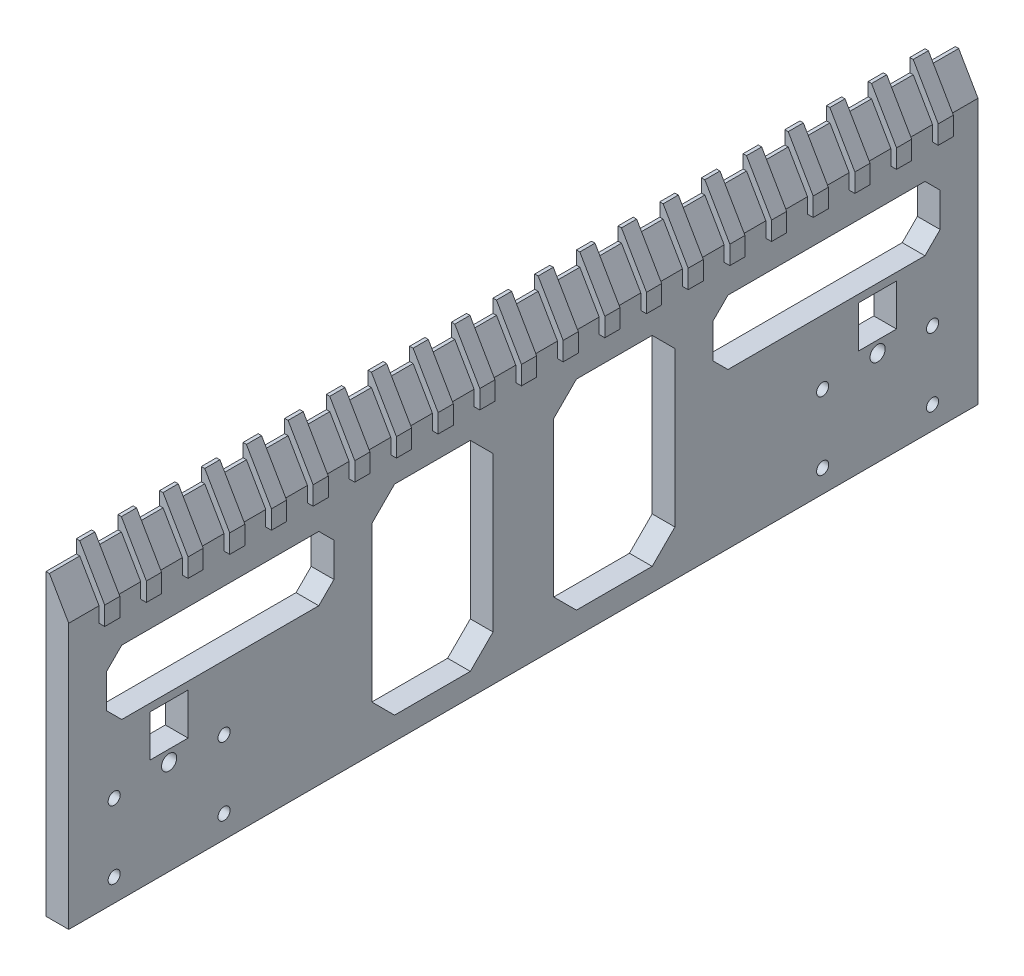
SolidWorks part; units mm, degrees
ref_plane "前视基准面" through (0, 0, 0) normal (0, 0, 1) x (1, 0, 0)
ref_plane "上视基准面" through (0, 0, 0) normal (0, 1, 0) x (1, 0, 0)
ref_plane "右视基准面" through (0, 0, 0) normal (1, 0, 0) x (0, 0, -1)
sketch "草图1" plane through (0, 0, 0) normal (1, 0, 0) x (0, 0, -1)
  line L1 (0, 0) -> (240, 0)
  line L2 (0, 0) -> (0, -70)
  line L3 (0, -70) -> (240, -70)
  line L4 (240, 0) -> (240, -70)
  dimension "D1" = 240
  dimension "D2" = 70
extrude "凸台-拉伸1" add sketch "草图1" along normal blind 6
sketch "草图3" plane through (6, 0, 0) normal (1, 0, 0) x (0, 0, -1)
  line L0 (120, 0) -> (120, -70) construction
  line L1 (14, -12) -> (66, -12)
  line L2 (10, -16) -> (10, -25)
  line L3 (14, -29) -> (66, -29)
  line L4 (70, -16) -> (70, -25)
  line L5 (240, 0) -> (0, 0) construction
  line L6 (0, -70) -> (240, -70) construction
  line L7 (0, 0) -> (0, -70) construction
  line L12 (10, -16) -> (14, -12)
  line L13 (10, -25) -> (14, -29)
  line L14 (66, -29) -> (70, -25)
  line L15 (66, -12) -> (70, -16)
  line L28 (80, -17.2) -> (86, -11.2)
  line L42 (86, -11.2) -> (106, -11.2)
  line L43 (80, -17.2) -> (80, -58)
  line L44 (86, -64) -> (106, -64)
  line L45 (112, -17.2) -> (112, -58)
  line L46 (106, -11.2) -> (112, -17.2)
  line L47 (106, -64) -> (112, -58)
  line L48 (80, -58) -> (86, -64)
  point P0 (10, -12)
  point P1 (70, -29)
  point P2 (10, -29)
  point P3 (70, -12)
  point P20 (80, -11.2)
  point P21 (112, -64)
  point P22 (80, -64)
  point P23 (112, -11.2)
  dimension "D1" = 10
  dimension "D2" = 12
  dimension "D3" = 17
  dimension "D4" = 60
  dimension "D5" = 11.2
  dimension "D6" = 6
  dimension "D7" = 52.8
  dimension "D12" = 80
  dimension "D13" = 8
  dimension "D14" = 32
extrude "切除-拉伸2" cut sketch "草图3" against normal through all
sketch "草图2" plane through (0, 0, 0) normal (1, 0, 0) x (0, 0, -1)
  line L0 (0, 0) -> (0, -70) construction
  line L1 (12, -46) -> (41, -46) construction
  line L2 (12, -46) -> (12, -64) construction
  line L3 (12, -64) -> (41, -64) construction
  line L4 (41, -46) -> (41, -64) construction
  line L5 (240, 0) -> (0, 0) construction
  line L6 (120, 0) -> (120, -70) construction
  circle A0 centre (12, -46) radius 1.55
  circle A1 centre (41, -64) radius 1.55
  circle A2 centre (41, -46) radius 1.55
  circle A3 centre (12, -64) radius 1.55
  dimension "D5" = 3.1
  dimension "D1" = 12
  dimension "D2" = 46
  dimension "D3" = 29
  dimension "D4" = 18
sketch "草图6" plane through (0, 0, 0) normal (0, 0, 1) x (1, 0, 0)
  line L0 (6, 0) -> (0, 0)
  line L1 (0, 0) -> (0, 8.8335)
  line L2 (0.9, 8.8335) -> (6, 0)
  line L3 (0, 8.8335) -> (0.9, 8.8335)
  line L4 (0, 8.8335) -> (0, 10.3923) construction
  line L5 (0, 10.3923) -> (0.9, 8.8335) construction
  dimension "D1" = 30
  dimension "D2" = 0.9
extrude "凸台-拉伸2" add sketch "草图6" against normal blind 240
ref_plane "基准面1" through (0, 0, -120) normal (0, 0, 1) x (1, 0, 0)
sketch "草图8" plane through (0, 0, -120) normal (0, 0, 1) x (1, 0, 0)
  line L0 (0, 10.3923) -> (0, 12.3335)
  line L1 (0.9, 12.3335) -> (7.5, 0.9019)
  line L2 (7.5, 0.9019) -> (7.5, -4)
  line L3 (7.5, -4) -> (6, -4)
  line L4 (6, 0) -> (6, -70) construction
  line L5 (6, -4) -> (6, 0)
  line L6 (6, 0) -> (0.9, 8.8335) construction
  line L7 (6, 0) -> (0.9, 8.8335)
  line L8 (0, 12.3335) -> (0.9, 12.3335)
  line L9 (0, 12.3335) -> (0, 13.8923) construction
  line L10 (0, 13.8923) -> (0.9, 12.3335) construction
  line L11 (0, 10.3923) -> (0, 8.8335)
  line L12 (0, 8.8335) -> (0.9, 8.8335)
  line L13 (0.9, 8.8335) -> (0, 10.3923) construction
  dimension "D1" = 3.5
  dimension "D2" = 1.5
  dimension "D3" = 4
  dimension "D4" = 0.9
extrude "凸台-拉伸3" add sketch "草图8" along normal mid plane 4
pattern_linear "阵列(线性)1" count 11 spacing 11 along (0, 0, 1) count 11 spacing 11 along (0, 0, -1) of "凸台-拉伸3"
hole_wizard "打孔尺寸(%根据)内六角圆柱头螺钉的类型1" positions "草图14" profile "草图15" counterbore size "M3" standard "GB" end condition through all
sketch "草图14" plane through (0, 0, 0) normal (-1, 0, 0) x (0, 0, 1)
  point P0 (-41, -46)
  point P3 (-12, -46)
  point P6 (-12, -64)
  point P9 (-41, -64)
sketch "草图15" plane through (0, -46, -41) normal (0, 1, 0) x (0, 0, 1)
  line L0 (0, 0) -> (0, 7.5)
  line L1 (0, 7.5) -> (1.6, 7.5)
  line L3 (1.6, 7.5) -> (1.6, 3.4)
  line L4 (1.6, 3.4) -> (3, 3.4)
  line L5 (3, 3.4) -> (3, 0)
  line L7 (3, 0) -> (0, 0)
  line L11 (0, -6.35) -> (0, 107.95) construction
  dimension "通孔孔直径" = 3.2
  dimension "通孔孔深度" = 7.5
  dimension "柱形沉头孔直径" = 6
  dimension "柱形沉头孔深度" = 3.4
sketch "草图16" plane through (0, 0, 0) normal (-1, 0, 0) x (0, 0, 1)
  line L0 (-12, -46) -> (-41, -46) construction
  line L1 (-26.5, -46) -> (-26.5, -29) construction
  line L2 (-14, -29) -> (-66, -29) construction
  line L3 (-26.5, -46) -> (-26.5, -70) construction
  line L4 (0, -70) -> (-240, -70) construction
  circle A0 centre (-26.5, -45.0233) radius 2
  dimension "D1" = 4
extrude "切除-拉伸3" cut sketch "草图16" against normal blind 10
mirror "镜向1" about plane through (0, 0, -120) normal (0, 0, 1) of "打孔尺寸(%根据)内六角圆柱头螺钉的类型1"
mirror "镜向2" about plane through (0, 0, -120) normal (0, 0, 1) of "切除-拉伸3", "切除-拉伸2"
sketch "草图17" plane through (0, 0, 0) normal (-1, 0, 0) x (0, 0, 1)
  line L0 (0, 8.8335) -> (0, -70) construction
  line L1 (-31.5, -31) -> (-21.5, -31)
  line L2 (-31.5, -31) -> (-31.5, -42)
  line L3 (-31.5, -42) -> (-21.5, -42)
  line L4 (-21.5, -31) -> (-21.5, -42)
  line L6 (0, -70) -> (-240, -70) construction
  line L7 (-120, -70) -> (-120, -8.018) construction
  line L8 (-208.5, -31) -> (-218.5, -31)
  line L9 (-208.5, -31) -> (-208.5, -42)
  line L10 (-208.5, -42) -> (-218.5, -42)
  line L11 (-218.5, -31) -> (-218.5, -42)
  dimension "D1" = 10
  dimension "D2" = 11
  dimension "D3" = 21.5
  dimension "D4" = 28
extrude "切除-拉伸4" cut sketch "草图17" against normal through all
